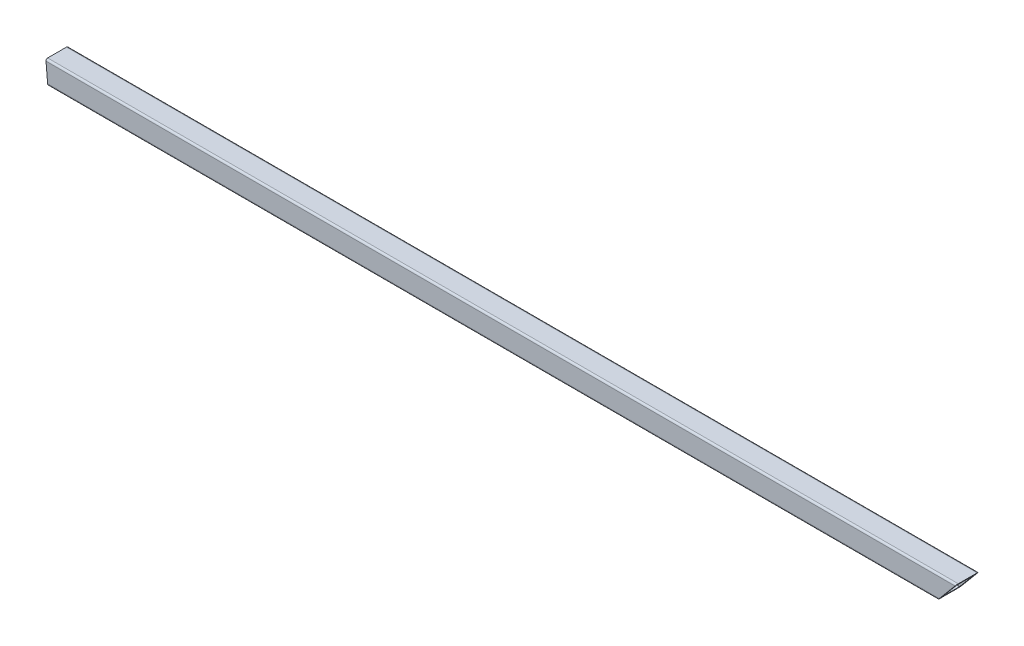
SolidWorks part; units mm, degrees
material "Plain Carbon Steel"
ref_plane "Front Plane" through (0, 0, 0) normal (0, 0, 1) x (1, 0, 0)
ref_plane "Top Plane" through (0, 0, 0) normal (0, 1, 0) x (1, 0, 0)
ref_plane "Right Plane" through (0, 0, 0) normal (1, 0, 0) x (0, 0, -1)
sketch "Sketch1" plane through (0, 0, 0) normal (1, 0, 0) x (0, 0, -1)
  line L0 (0, 2.54) -> (0, 29.21)
  line L1 (-2.54, 31.75) -> (-29.21, 31.75)
  line L2 (-31.75, 29.21) -> (-31.75, 2.54)
  line L3 (-29.21, 0) -> (-2.54, 0)
  line L4 (-4.1275, 4.1275) -> (-4.1275, 27.6225)
  line L5 (-4.1275, 27.6225) -> (-27.6225, 27.6225)
  line L6 (-27.6225, 27.6225) -> (-27.6225, 4.1275)
  line L7 (-27.6225, 4.1275) -> (-4.1275, 4.1275)
  arc A0 (-31.75, 2.54) -> (-29.21, 0) centre (-29.21, 2.54) ccw
  arc A1 (0, 2.54) -> (-2.54, 0) centre (-2.54, 2.54) cw
  arc A2 (0, 29.21) -> (-2.54, 31.75) centre (-2.54, 29.21) ccw
  arc A3 (-31.75, 29.21) -> (-29.21, 31.75) centre (-29.21, 29.21) cw
  arc A4 (-4.1275, 27.6225) -> (-4.1275, 27.6225) centre (-4.1275, 27.6225) ccw
  arc A5 (-27.6225, 27.6225) -> (-27.6225, 27.6225) centre (-27.6225, 27.6225) cw
  arc A6 (-27.6225, 4.1275) -> (-27.6225, 4.1275) centre (-27.6225, 4.1275) ccw
  arc A7 (-4.1275, 4.1275) -> (-4.1275, 4.1275) centre (-4.1275, 4.1275) cw
  point P12 (0, 0)
  point P15 (0, 31.75)
  point P18 (-31.75, 31.75)
  dimension "D3" = 2.54
  dimension "D1" = 31.75
  dimension "D2" = 31.75
  dimension "D4" = 4.1275
extrude "Boss-Extrude1" add sketch "Sketch1" along normal blind 1320.8
scale "Scale4" bodies to scale 101 scale about centroid uniform scaling no x scale factor 1 y scale factor 0.4 z scale factor 0.4
sketch "Sketch4" plane through (0, 0, 9.525) normal (0, 0, 1) x (1, 0, 0)
  line L0 (1311.5819, 15.875) -> (894.3272, 15.875) construction
  line L1 (1320.8, 21.209) -> (670.0204, 21.209) construction
  line L2 (1320.8, 10.541) -> (669.1796, 10.541) construction
sketch "Sketch8" plane through (0, 0, 22.225) normal (0, 0, 1) x (1, 0, 0)
  line L0 (515.7051, 22.225) -> (505.0485, 9.525)
  line L1 (1320.8, 22.225) -> (0, 22.225) construction
  line L2 (347.867, -177.7966) -> (591.4116, 112.4485) construction
  line L3 (1320.8, 9.525) -> (0, 9.525) construction
  line L4 (505.0485, 9.525) -> (644.1921, 9.525)
  line L5 (644.1921, 9.525) -> (654.8487, 22.225)
  line L6 (654.8487, 22.225) -> (515.7051, 22.225)
  line L7 (0, 22.225) -> (1.1111, 9.525)
  line L8 (1.1111, 9.525) -> (0, 9.525)
  line L9 (0, 9.525) -> (0, 22.225)
  dimension "D1" = 5
extrude "Cut-Extrude2" cut sketch "Sketch8" against normal through all
